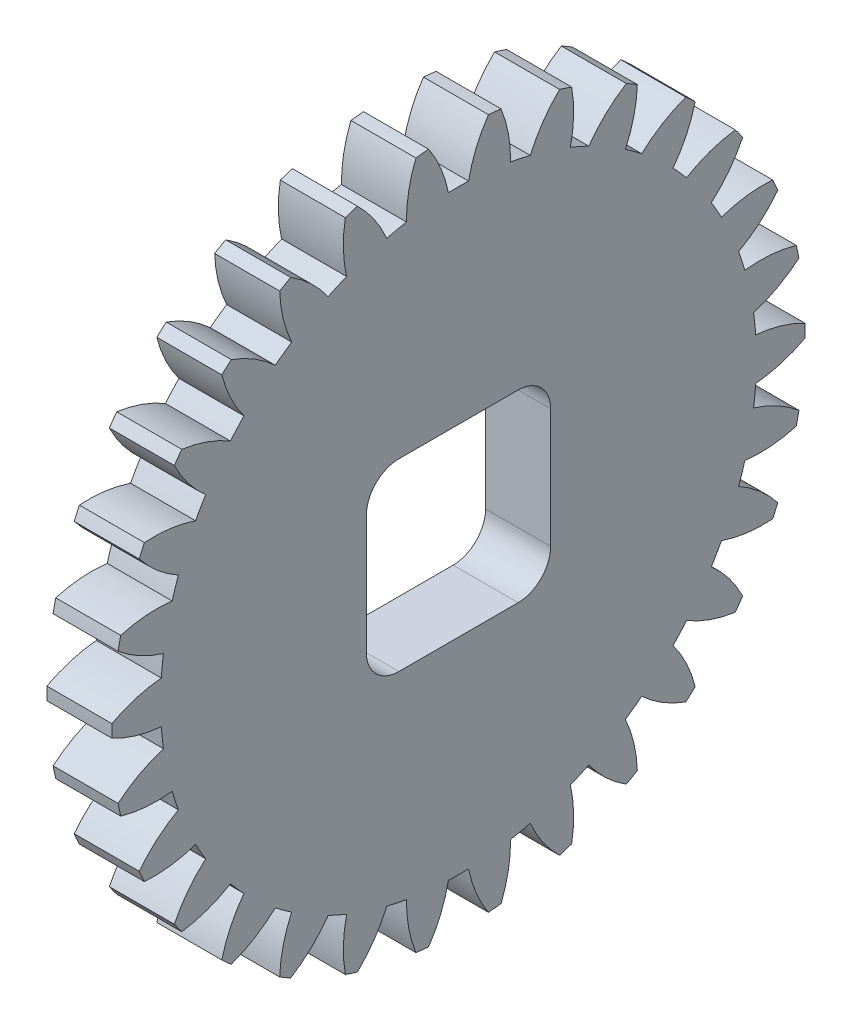
SolidWorks part; units mm, degrees
material "ﾎﾟﾘｵｷｼﾒﾁﾚﾝ(POM)ｱｾﾀｰﾙ共重合体"
ref_plane "Plane1" through (0, 0, 0) normal (0, 0, 1) x (1, 0, 0)
ref_plane "Plane2" through (0, 0, 0) normal (0, 1, 0) x (1, 0, 0)
ref_plane "Plane3" through (0, 0, 0) normal (1, 0, 0) x (0, 0, -1)
other "Configuration Table"
sketch "HoldingSke" plane through (0, 0, 0) normal (0, 1, 0) x (1, 0, 0)
  line L0 (0, 0) -> (0.866, -0.5)
  line L1 (-15, 0) -> (100, 0) construction
  line L2 (0, 0) -> (-2.1039, 2.3779)
  line L3 (0, 0) -> (-11.863, 4.5341)
  line L4 (0, 0) -> (7.479, 4.318)
  line L5 (0, 0) -> (-46.8476, -17.4728)
  line L6 (0, 0) -> (-2.4869, -1.6779)
  line L7 (-2.1039, 2.3779) -> (8.6586, 51.2059)
  line L8 (-76.2, 54.61) -> (-75.2, 54.61)
  line L9 (-71.009, 38.7566) -> (-53.1078, 45.2721)
  line L10 (-76.2, 71.12) -> (104.1128, 71.12)
  line L11 (0, 0) -> (-3, 0)
  line L12 (-76.2, 101.6) -> (-76.162, 101.6)
  line L13 (24.9733, 27.94) -> (52.9518, 28.4284)
  line L14 (24.9733, 27.94) -> (24.9743, 27.94)
  line L15 (24.9733, 27.94) -> (100.4006, 29.5858)
  line L16 (-63.627, -1) -> (-12.827, -1)
  circle A0 centre (0, 0) radius 4
  circle A1 centre (0, 0) radius 13.749
  circle A2 centre (0, 0) radius 37.5
  circle A3 centre (0, 0) radius 4
  dimension "MHD" = 27.498
  dimension "Hub_dia" = 75
  dimension "Bore" = 8
  dimension "MBD" = 8
  dimension "Num_teeth" = 30
  dimension "Pitch" = 1
  dimension "Overall_len" = 50
  dimension "Show_teeth" = 30
  dimension "Thickness" = 3
  dimension "OAL" = 50.0001
  dimension "T_dim" = 1
  dimension "Ap" = 20
  dimension "H" = 19.05
  dimension "Pitch_radius" = 180.3128
  dimension "Width" = 3
  dimension "Backlash" = 0.038
  dimension "Addendum_fac" = 1
  dimension "Dedendum_fac" = 1.25
  dimension "Clearance_fac" = 0.25
  dimension "Dedendum_add" = 0.001
  dimension "Module" = 1
sketch "BasProSke" plane through (0, 0, 0) normal (0, 1, 0) x (1, 0, 0)
  line L0 (-10, 0) -> (60, 0) construction
  line L1 (0, 0) -> (0, 16)
  line L2 (0, 0) -> (3, 0)
  line L3 (3, 0) -> (3, 16)
  line L4 (3, 16) -> (0, 16)
  dimension "Thickness" = 3
  dimension "Diameter" = 32
revolve "Base-Revolve" add sketch "BasProSke" angle 360 about L0
sketch "TooCutSke" plane through (0, 0, 0) normal (1, 0, 0) x (0, 0, -1)
  line L1 (0, 0) -> (0, 107) construction
  line L2 (0, 0) -> (-0.8515, 14.9758) construction
  line L3 (0, 0) -> (-3.1323, 29.8014) construction
  line L4 (-0.8515, 14.9758) -> (-1.5661, 14.9007) construction
  arc A0 (0.4664, 13.7411) -> (-0.4664, 13.7411) centre (0, 0) ccw
  arc A1 (1.3975, 15.9644) -> (-1.3975, 15.9644) centre (0, 0) ccw
  circle A2 centre (0, 0) radius 15 construction
  circle A3 centre (0, 0) radius 14.0954 construction
  arc A4 (-0.4664, 13.7411) -> (-1.3975, 15.9644) centre (-6.3534, 12.5823) ccw
  arc A5 (1.3975, 15.9644) -> (0.4664, 13.7411) centre (6.3534, 12.5823) ccw
  dimension "Root_dia" = 27.498
  dimension "Overcut_dia" = 32.0508
  dimension "Pitch_dia" = 30
  dimension "Base_dia" = 28.1908
  dimension "Flank_rad" = 6
  dimension "Half_ang" = 6
  dimension "Half_CT" = 0.7185
extrude "ToothCut" cut sketch "TooCutSke" along normal through all
fillet "Breaks" [suppressed] radius 0.02 tangent propagation no
fillet "RootFillets" [suppressed] radius 0.251
pattern_circular "TeethCuts" count 30 every 12 about axis through (-10, 0, 0) along (1, 0, 0) of "ToothCut", "RootFillets", "Breaks"
sketch "HubNeaOneSke" plane through (0, 0, 0) normal (-1, 0, 0) x (0, 0, 1)
  circle A0 centre (0, 0) radius 13.749
  dimension "Diameter" = 27.498
extrude "HubNearOne" [suppressed] add sketch "HubNeaOneSke" along normal blind 47.0001
sketch "HubNeaBotSke" plane through (0, 0, 0) normal (-1, 0, 0) x (0, 0, 1)
  circle A0 centre (0, 0) radius 13.749
  dimension "Diameter" = 27.498
extrude "HubNearBoth" [suppressed] add sketch "HubNeaBotSke" along normal blind 23.5
ref_plane "FarPln" through (3, 0, 0) normal (1, 0, 0) x (0, 0, -1)
sketch "HubFarSke" plane through (3, 0, 0) normal (1, 0, 0) x (0, 0, -1)
  circle A0 centre (0, 0) radius 13.749
  dimension "Diameter" = 27.498
extrude "HubFar" [suppressed] add sketch "HubFarSke" along normal blind 23.5
sketch "BorSke" plane through (0, 0, 0) normal (1, 0, 0) x (0, 0, -1)
  circle A0 centre (0, 0) radius 4
  dimension "Diameter" = 8
extrude "Bore" cut sketch "BorSke" along normal mid plane 100.0001
sketch "KeySke" plane through (0, 0, 0) normal (1, 0, 0) x (0, 0, -1)
  line L0 (-1, 0) -> (-1, 5)
  line L1 (-1, 5) -> (1, 5)
  line L2 (1, 5) -> (1, 0)
  line L3 (0, 0) -> (0, 34) construction
  line L4 (-1, 0) -> (1, 0)
  dimension "Offset" = 5
  dimension "Width" = 2
extrude "Keyway" [suppressed] cut sketch "KeySke" along normal mid plane 100.0001
pattern_circular "Keyway2" [suppressed] count 2 every 90 about axis through (-10, 0, 0) along (1, 0, 0) reverse direction yes
sketch "ｽｹｯﾁ1" plane through (0, 0, 0) normal (-1, 0, 0) x (0, 0, 1)
  circle A0 centre (0, 0) radius 4 construction
  circle A1 centre (0, 0) radius 4
extrude "ﾎﾞｽ - 押し出し1" add sketch "ｽｹｯﾁ1" against normal up to surface (3 mm away) up to face at (3, 0, 4)
sketch "ｽｹｯﾁ2" plane through (0, 0, 0) normal (-1, 0, 0) x (0, 0, 1)
  circle A0 centre (0, 0) radius 2
  dimension "D1" = 4
extrude "ｶｯﾄ - 押し出し1" cut sketch "ｽｹｯﾁ2" against normal through all
sketch "ｽｹｯﾁ3" plane through (3, 0, 0) normal (1, 0, 0) x (0, 0, -1)
  line L1 (-2.75, 4.25) -> (2.75, 4.25)
  line L2 (-4.25, 2.75) -> (-4.25, -2.75)
  line L3 (-2.75, -4.25) -> (2.75, -4.25)
  line L4 (4.25, 2.75) -> (4.25, -2.75)
  line L5 (-4.25, 4.25) -> (4.25, -4.25) construction
  line L6 (-4.25, -4.25) -> (4.25, 4.25) construction
  arc A0 (2.75, -4.25) -> (4.25, -2.75) centre (2.75, -2.75) ccw
  arc A1 (2.75, 4.25) -> (4.25, 2.75) centre (2.75, 2.75) cw
  arc A2 (-4.25, -2.75) -> (-2.75, -4.25) centre (-2.75, -2.75) ccw
  arc A3 (-2.75, 4.25) -> (-4.25, 2.75) centre (-2.75, 2.75) ccw
  point P0 (0, 0)
  dimension "D3" = 1.5
  dimension "D1" = 8.5
  dimension "D2" = 8.5
extrude "ｶｯﾄ - 押し出し2" cut sketch "ｽｹｯﾁ3" against normal blind 10
equation "' \"Module@HoldingSke\" = 6.35"
equation "' \"Num_teeth@HoldingSke\" = 12"
equation "' \"Ap@HoldingSke\" =  20"
equation "' \"Ap@HoldingSke\" = 20"
equation "' \"Width@HoldingSke\" = 0.5 * 25.4"
equation "' \"Hub_dia@HoldingSke\"= 1 * 25.4"
equation "' \"Hub_dia@HoldingSke\" = 1 * 25.4"
equation "' \"Overall_len@HoldingSke\" = 1.0 * 25.4"
equation "' \"Bore@HoldingSke\" = 0.75 * 25.4"
equation "' \"T_dim@HoldingSke\" = 0.1 * 25.4"
equation "' \"Width@KeySke\" = 0.25 * 25.4"
equation "' \"Show_teeth@HoldingSke\" = 13"
equation "' \"Backlash@HoldingSke\" = 0.009 * 25.4"
equation "' \"Addendum_fac@HoldingSke\" = 1.0"
equation "' \"Dedendum_fac@HoldingSke\" = 1.25"
equation "' \"Dedendum_add@HoldingSke\" = 0.00005 * 25.4"
equation "' \"Clearance_fac@HoldingSke\" = 0.25"
equation "\"Pitch@HoldingSke\" = 1 / \"Module@HoldingSke\""
equation "\"Overcut_dia@TooCutSke\" = (\"Num_teeth@HoldingSke\" + 2 * \"Addendum_fac@HoldingSke\") / \"Pitch@HoldingSke\" + 0.002 * 25.4"
equation "\"Pitch_dia@TooCutSke\" = \"Num_teeth@HoldingSke\" / \"Pitch@HoldingSke\""
equation "\"Base_dia@TooCutSke\" = \"Num_teeth@HoldingSke\" / \"Pitch@HoldingSke\" * cos((\"Ap@HoldingSke\"  * 3.14159265 / 180))"
equation "\"Root_dia@TooCutSke\" = (\"Num_teeth@HoldingSke\" + 2) / \"Pitch@HoldingSke\" - 2 * (\"Addendum_fac@HoldingSke\" + \"Dedendum_fac@HoldingSke\") / \"Pitch@HoldingSke\" - \"Dedendum_add@HoldingSke\" * 2"
equation "\"Half_ang@TooCutSke\" = 180 / \"Num_teeth@HoldingSke\""
equation "\"Half_CT@TooCutSke\" = \"Num_teeth@HoldingSke\" / \"Pitch@HoldingSke\" * sin((3.14159265 / 2 / \"Num_teeth@HoldingSke\")) / 2 - 7 * \"Backlash@HoldingSke\" / 4"
equation "\"Flank_rad@TooCutSke\" = \"Num_teeth@HoldingSke\" / \"Pitch@HoldingSke\" / 5"
equation "\"Radius@RootFillets\" = \"Clearance_fac@HoldingSke\" / \"Pitch@HoldingSke\" + \"Dedendum_add@HoldingSke\""
equation "\"Break_rad@Breaks\" = 0.02 / \"Pitch@HoldingSke\""
equation "\"Thickness@HoldingSke\" = \"Width@HoldingSke\""
equation "\"OAL@HoldingSke\" = \"Thickness@HoldingSke\""
equation "\"MHD@HoldingSke\" = (\"Num_teeth@HoldingSke\" + 2) / \"Pitch@HoldingSke\" - 2 * (\"Addendum_fac@HoldingSke\" + \"Dedendum_fac@HoldingSke\")  / \"Pitch@HoldingSke\" - \"Dedendum_add@HoldingSke\" * 2"
equation "\"MBD@HoldingSke\" = (\"Num_teeth@HoldingSke\" + 2) / \"Pitch@HoldingSke\" - 2 * (\"Addendum_fac@HoldingSke\" + \"Dedendum_fac@HoldingSke\")  / \"Pitch@HoldingSke\" - \"Dedendum_add@HoldingSke\" * 2 - 0.002 * 25.4"
equation "\"MHD@HoldingSke\" = ((sgn( \"MHD@HoldingSke\" - \"Hub_dia@HoldingSke\" )-1)*( \"MHD@HoldingSke\" - \"Hub_dia@HoldingSke\" ))/-2+ \"Hub_dia@HoldingSke\""
equation "\"MBD@HoldingSke\" = ((sgn( \"MBD@HoldingSke\" - \"Bore@HoldingSke\" )-1)*( \"MBD@HoldingSke\" - \"Bore@HoldingSke\" ))/-2+ \"Bore@HoldingSke\""
equation "\"OAL@HoldingSke\" = ((sgn( \"OAL@HoldingSke\" - \"Overall_len@HoldingSke\" )+1)*( \"OAL@HoldingSke\" - \"Overall_len@HoldingSke\" ))/2 + \"Overall_len@HoldingSke\" + 0.000002 * 25.4"
equation "\"Num_teeth@TeethCuts\" = int( \"Show_teeth@HoldingSke\" ) + 1"
equation "\"Num_teeth@TeethCuts\" = ((sgn( \"Num_teeth@TeethCuts\" - \"Num_teeth@HoldingSke\" )-1)*( \"Num_teeth@TeethCuts\" - \"Num_teeth@HoldingSke\" ))/-2+ \"Num_teeth@HoldingSke\""
equation "\"Num_teeth@TeethCuts\" = ((sgn( \"Num_teeth@TeethCuts\" - 2.0)+1)*( \"Num_teeth@TeethCuts\" - 2.0))/2 +2.0"
equation "\"Angle@TeethCuts\" = 360.0 / \"Num_teeth@HoldingSke\""
equation "\"Diameter@BasProSke\" = (\"Num_teeth@HoldingSke\" + 2 * \"Addendum_fac@HoldingSke\") / \"Pitch@HoldingSke\""
equation "\"Thickness@BasProSke\"  = \"Thickness@HoldingSke\""
equation "' \"Fillet_rad@BasProSke\" =  \"Thickness@HoldingSke\" * 0.05"
equation "' \"Fillet_rad@BasProSke\" = \"Thickness@HoldingSke\" * 0.05"
equation "\"MHD@HoldingSke\" = ((sgn( \"MHD@HoldingSke\" - \"Root_dia@TooCutSke\" )-1)*( \"MHD@HoldingSke\" - \"Root_dia@TooCutSke\" ))/-2+ \"Root_dia@TooCutSke\""
equation "\"Diameter@HubNeaOneSke\" = \"MHD@HoldingSke\""
equation "\"Length@HubNearOne\" = \"OAL@HoldingSke\" - \"Thickness@BasProSke\""
equation "\"Diameter@HubNeaBotSke\" = \"MHD@HoldingSke\""
equation "\"Length@HubNearBoth\" = ( \"OAL@HoldingSke\" - \"Thickness@BasProSke\" ) / 2.0"
equation "\"Thickness@FarPln\" = \"Thickness@BasProSke\""
equation "\"Diameter@HubFarSke\" = \"MHD@HoldingSke\""
equation "\"Length@HubFar\" = ( \"OAL@HoldingSke\" - \"Thickness@BasProSke\" ) / 2.0"
equation "\"Diameter@BorSke\" = \"MBD@HoldingSke\""
equation "\"D1@Bore\" = \"OAL@HoldingSke\" * 2.0"
equation "\"D1@Keyway\" = \"OAL@HoldingSke\" * 2.0"
equation "\"Offset@KeySke\" = \"T_dim@HoldingSke\" + \"MBD@HoldingSke\" / 2.0"
